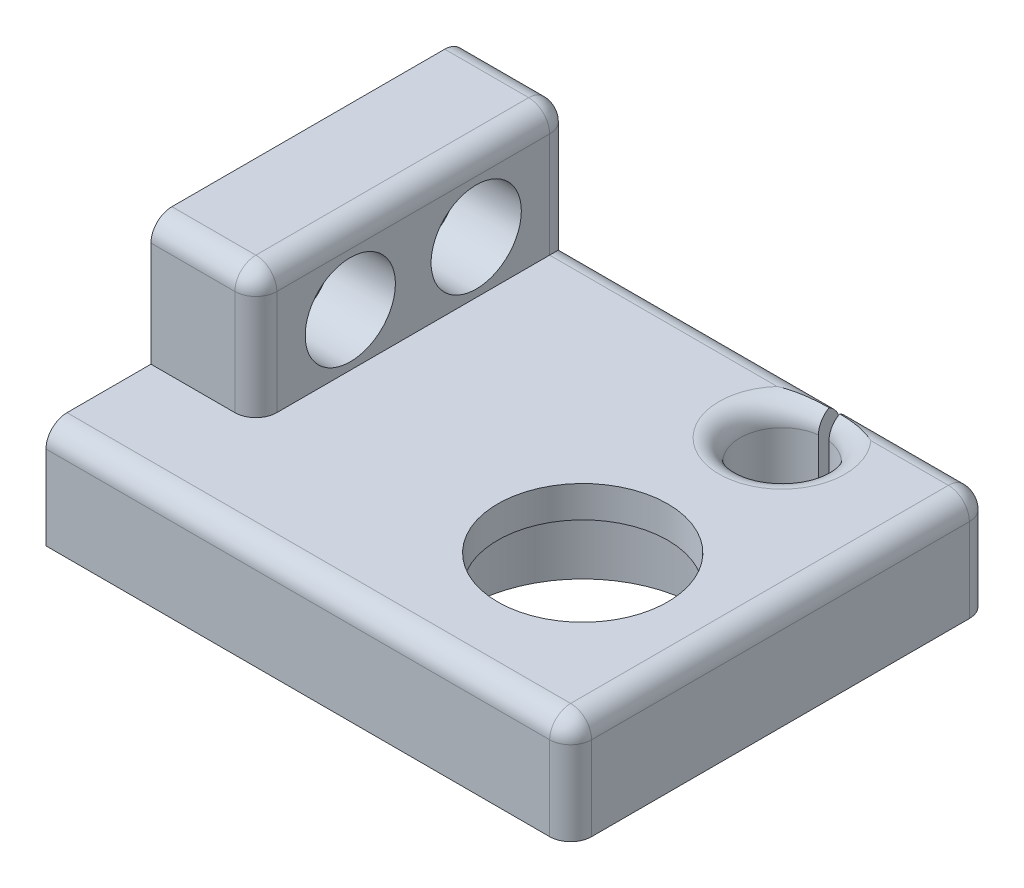
SolidWorks part; units mm, degrees
ref_plane "Front Plane" through (0, 0, 0) normal (0, 0, 1) x (1, 0, 0)
ref_plane "Top Plane" through (0, 0, 0) normal (0, 1, 0) x (1, 0, 0)
ref_plane "Right Plane" through (0, 0, 0) normal (1, 0, 0) x (0, 0, -1)
sketch "Sketch2" plane through (0, 0, 0) normal (0, 1, 0) x (1, 0, 0)
  line L0 (36.15, -6) -> (36.15, -25) construction
  line L1 (0, 0) -> (50, 0)
  line L2 (0, 0) -> (0, -40)
  line L3 (0, -40) -> (50, -40)
  line L4 (50, 0) -> (50, -40)
  line L5 (36.15, -2.0314) -> (36.15, -6) construction
  line L6 (35.65, 0) -> (36.65, 0)
  line L7 (35.65, 0) -> (35.65, -2.0314)
  line L8 (35.65, -2.0314) -> (36.65, -2.0314)
  line L9 (36.65, 0) -> (36.65, -2.0314)
  line L10 (36.15, -25) -> (36.15, -33.0846) construction
  line L12 (35.65, -40) -> (36.65, -40)
  line L13 (35.65, -40) -> (35.65, -33.0846) construction
  line L14 (35.65, -33.0846) -> (36.65, -33.0846)
  line L15 (36.65, -40) -> (36.65, -33.0846) construction
  circle A2 centre (36.15, -6) radius 4
  circle A3 centre (36.15, -25) radius 11.1 construction
  circle A4 centre (36.15, -25) radius 8.1
  dimension "D3" = 13.85
  dimension "D4" = 6
  dimension "D5" = 19
  dimension "D6" = 50
  dimension "D7" = 40
  dimension "D8" = 1
  dimension "D1" = 22.2
  dimension "D2" = 8
  dimension "D9" = 3
  dimension "D10" = 1
extrude "Boss-Extrude1" add sketch "Sketch2" along normal blind 10 contours L4 L1 L2 L3 A2 region at (23.3457, 0, 19.8342)
sketch "Sketch3" plane through (0, 0, 0) normal (0, -1, 0) x (1, 0, 0)
  circle A0 centre (36.15, 25) radius 11.1 construction
  circle A1 centre (36.15, 25) radius 11.1
  circle A2 centre (36.15, 25) radius 8.1
  circle A3 centre (36.15, 25) radius 8.1 construction
extrude "Cut-Extrude1" cut sketch "Sketch3" against normal blind 7
sketch "Sketch10" plane through (0, 0, 0) normal (0, 0, -1) x (-1, 0, 0)
  line L1 (0, 10) -> (-10, 10)
  line L2 (0, 10) -> (0, 22)
  line L3 (0, 22) -> (-10, 22)
  line L4 (-10, 10) -> (-10, 22)
  dimension "D1" = 12
  dimension "D2" = 10
extrude "Boss-Extrude5" add sketch "Sketch10" against normal blind 30
sketch "Sketch11" plane through (10, 0, 0) normal (1, 0, 0) x (0, 0, -1)
  line L0 (-21, 15) -> (-9, 15) construction
  line L1 (-9, 15) -> (0, 15) construction
  line L3 (-21, 15) -> (-30, 15) construction
  line L5 (0, 22) -> (0, 10) construction
  line L6 (-30, 22) -> (-30, 10) construction
  line L7 (0, 10) -> (-40, 10) construction
  circle A0 centre (-21, 15) radius 2.8
  circle A1 centre (-9, 15) radius 2.8
  dimension "D1" = 12
  dimension "D2" = 5.6
  dimension "D3" = 5
extrude "Cut-Extrude4" cut sketch "Sketch11" against normal through all
sketch "Sketch12" plane through (10, 0, 0) normal (1, 0, 0) x (0, 0, -1)
  circle A0 centre (-21, 15) radius 4.3
  circle A1 centre (-9, 15) radius 4.3
  dimension "D1" = 8.6
extrude "Cut-Extrude5" cut sketch "Sketch12" against normal blind 6
fillet "Fillet2" radius 2 12 edges at (22.825, 10, 0) (43.325, 10, 0) (5, 22, 0) (10, 16, 0) (10, 22, 15) (5, 22, 30) (10, 16, 30) (25, 10, 40) (50, 10, 20) (50, 5, 40) (50, 5, 0) (36.15, 10, 10)
